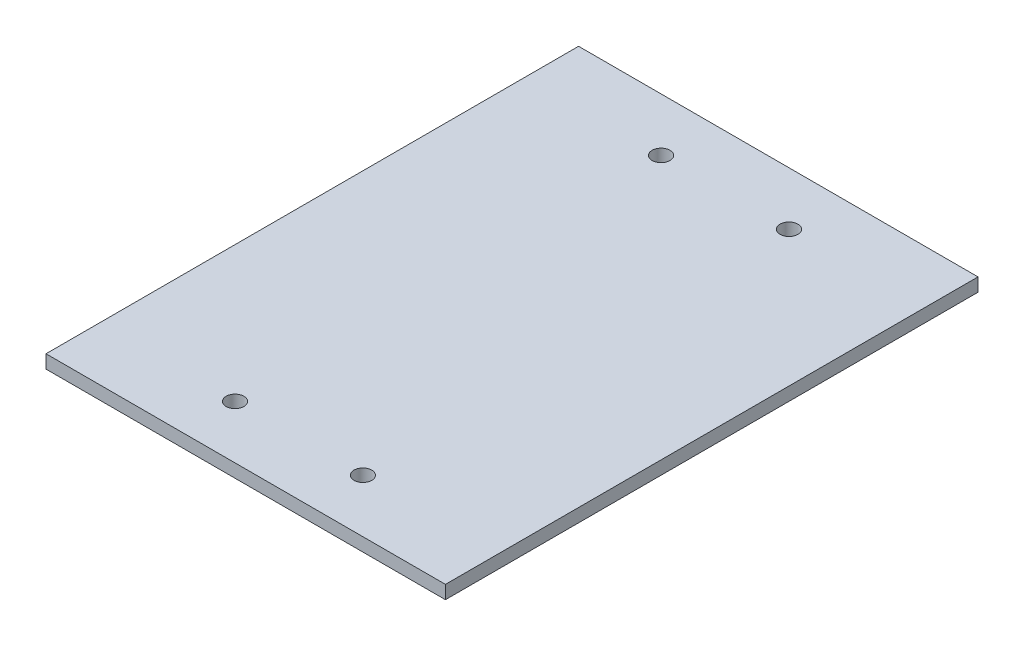
SolidWorks part; units mm, degrees
ref_plane "Front Plane" through (0, 0, 0) normal (0, 0, 1) x (1, 0, 0)
ref_plane "Top Plane" through (0, 0, 0) normal (0, 1, 0) x (1, 0, 0)
ref_plane "Right Plane" through (0, 0, 0) normal (1, 0, 0) x (0, 0, -1)
sketch "Sketch1" plane through (0, 0, 0) normal (0, 1, 0) x (1, 0, 0)
  line L0 (0, 50.8) -> (0, -50.8) construction
  line L1 (-38.1, 50.8) -> (38.1, 50.8)
  line L2 (-38.1, 50.8) -> (-38.1, -50.8)
  line L3 (-38.1, -50.8) -> (38.1, -50.8)
  line L4 (38.1, 50.8) -> (38.1, -50.8)
  line L5 (-38.1, 50.8) -> (38.1, -50.8) construction
  line L6 (-38.1, -50.8) -> (38.1, 50.8) construction
  line L7 (38.1, 0) -> (-38.1, 0) construction
  line L8 (-12.2, 40.64) -> (12.2, 40.64) construction
  circle A0 centre (-12.2, 40.64) radius 1.7
  circle A1 centre (12.2, 40.64) radius 1.7
  circle A2 centre (12.2, -40.64) radius 1.7
  circle A3 centre (-12.2, -40.64) radius 1.7
  point P0 (0, 0)
  point P14 (0, 40.64)
  dimension "D3" = 3.4
  dimension "D1" = 76.2
  dimension "D2" = 101.6
  dimension "D4" = 10.16
  dimension "D5" = 12.2
extrude "Boss-Extrude1" add sketch "Sketch1" along normal blind 2.54
